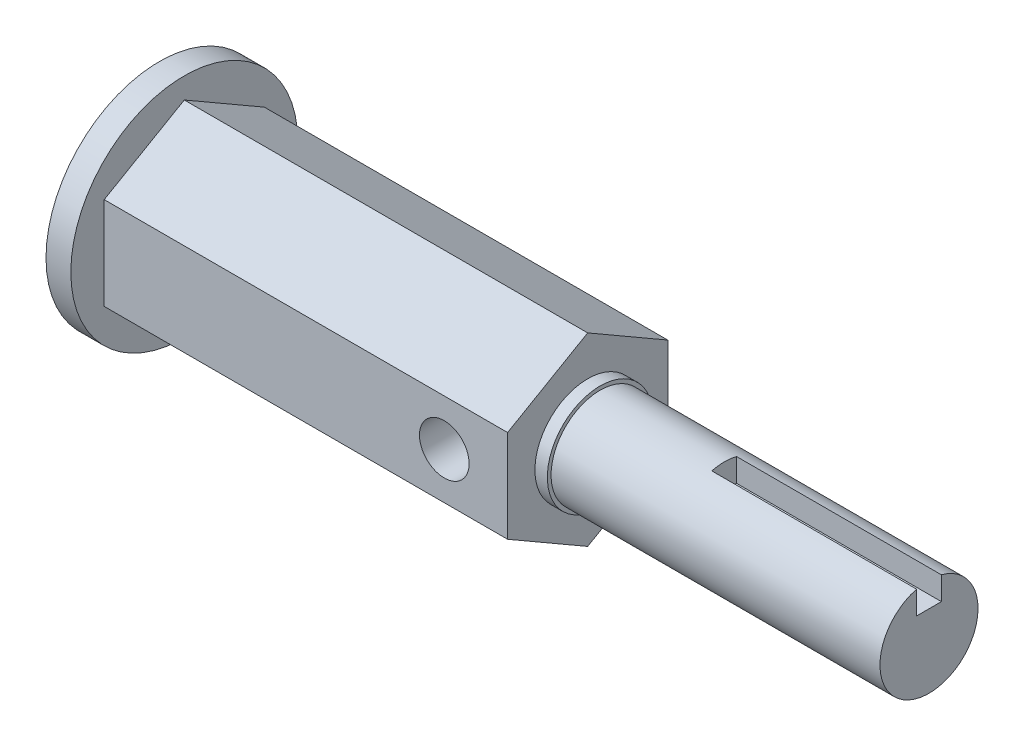
SolidWorks part; units mm, degrees
ref_plane "Front Plane" through (0, 0, 0) normal (1, 0, 0) x (0, 1, 0)
ref_plane "Top Plane" through (0, 0, 0) normal (0, 0, 1) x (0, 1, 0)
ref_plane "Right Plane" through (0, 0, 0) normal (0, 1, 0) x (-1, 0, 0)
sketch "Sketch1" plane through (0, 0, 0) normal (1, 0, 0) x (0, 1, 0)
  circle A0 centre (0, 0) radius 3.95
  dimension "D1" = 7.9
extrude "Boss-Extrude1" add sketch "Sketch1" along normal blind 60
sketch "Sketch2" plane through (0, 0, 0) normal (-1, 0, 0) x (0, -1, 0)
  circle A0 centre (0, 0) radius 9.141
  dimension "D1" = 18.282
extrude "Boss-Extrude2" add sketch "Sketch2" along normal blind 2
sketch "Sketch3" plane through (0, 0, 0) normal (1, 0, 0) x (0, 1, 0)
  line L1 (3.725, 6.4519) -> (-3.725, 6.4519)
  line L2 (-3.725, 6.4519) -> (-7.45, 0)
  line L3 (-7.45, 0) -> (-3.725, -6.4519)
  line L4 (-3.725, -6.4519) -> (3.725, -6.4519)
  line L5 (3.725, -6.4519) -> (7.45, 0)
  line L6 (7.45, 0) -> (3.725, 6.4519)
  circle A0 centre (0, 0) radius 6.4519 construction
  dimension "D2" = 12.9038
  dimension "D1" = 7.45
extrude "Boss-Extrude3" add sketch "Sketch3" along normal blind 32.5
sketch "Sketch4" plane through (60, 0, 0) normal (1, 0, 0) x (0, 1, 0)
  line L0 (1.95, -1) -> (1.95, 1)
  line L1 (1.95, -1) -> (3.95, -1)
  line L3 (1.95, 1) -> (3.95, 1)
  line L4 (3.95, -1) -> (3.95, 1)
  line L5 (0, 0) -> (3.95, 0) construction
  circle A0 centre (0, 0) radius 3.95 construction
  point P4 (3.95, 0)
  dimension "D1" = 2
  dimension "D2" = 2
extrude "Cut-Extrude1" cut sketch "Sketch4" against normal blind 16.5
sketch "Sketch5" plane through (32.5, 0, 0) normal (1, 0, 0) x (0, 1, 0)
  circle A0 centre (0, 0) radius 4.25
  dimension "D1" = 8.5
extrude "Boss-Extrude5" add sketch "Sketch5" along normal blind 1
sketch "Sketch6" plane through (0, 0, -6.4519) normal (0, 0, -1) x (1, 0, 0)
  line L0 (0, 0) -> (25.4, 0) construction
  line L1 (25.4, 0) -> (27.4, 0) construction
  circle A0 centre (27.4, 0) radius 2
  dimension "D1" = 25.4
  dimension "D2" = 4
extrude "Cut-Extrude2" cut sketch "Sketch6" against normal through all
